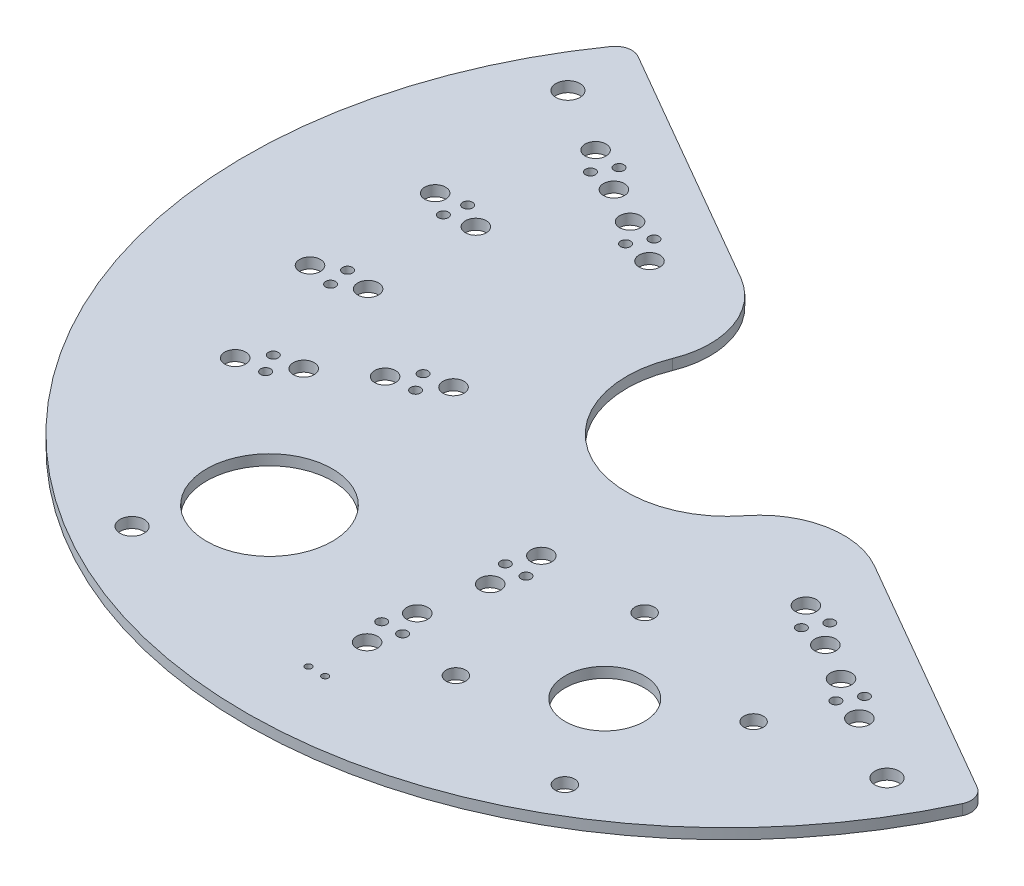
SolidWorks part; units mm, degrees
ref_plane "Front Plane" through (0, 0, 0) normal (0, 0, 1) x (1, 0, 0)
ref_plane "Top Plane" through (0, 0, 0) normal (0, 1, 0) x (1, 0, 0)
ref_plane "Right Plane" through (0, 0, 0) normal (1, 0, 0) x (0, 0, -1)
sketch "Sketch1" plane through (0, 0, 0) normal (0, 1, 0) x (1, 0, 0)
  line L0 (0, 50.8) -> (0, 59.6199) construction
  line L1 (0, 50.8) -> (11.3081, 50.8) construction
  line L2 (0, 0) -> (0, 47) construction
  line L3 (0, 0) -> (-46.286, 8.1615) construction
  line L4 (0, 0) -> (0, 47) construction
  line L5 (0, 0) -> (-46.286, -8.1615) construction
  line L6 (-30.1951, -16.4814) -> (-38.7564, -18.616) construction
  line L7 (1.7716, -33.8648) -> (4.3514, -25.4269) construction
  line L8 (31.2901, -20.38) -> (25.051, -14.141) construction
  line L9 (-31.8057, 17.1605) -> (-38.0448, 23.3996) construction
  circle A0 centre (0, 0) radius 50.8 construction
  circle A1 centre (0, 0) radius 15.24
  circle A2 centre (0, 0) radius 73.025
  circle A3 centre (0, 50.8) radius 6.3 construction
  circle A4 centre (25.4, 43.9941) radius 6.3 construction
  circle A5 centre (43.9941, 25.4) radius 6.3 construction
  circle A6 centre (50.8, 0) radius 6.3 construction
  circle A7 centre (43.9941, -25.4) radius 6.3 construction
  circle A8 centre (25.4, -43.9941) radius 6.3 construction
  circle A9 centre (0, -50.8) radius 6.3 construction
  circle A10 centre (-25.4, -43.9941) radius 6.3 construction
  circle A11 centre (-43.9941, -25.4) radius 6.3 construction
  circle A12 centre (-50.8, 0) radius 6.3 construction
  circle A13 centre (-43.9941, 25.4) radius 6.3 construction
  circle A14 centre (-25.4, 43.9941) radius 6.3 construction
  circle A15 centre (0, 50.8) radius 1.585 construction
  circle A16 centre (-1.585, 50.8) radius 0.75
  circle A17 centre (1.585, 50.8) radius 0.75
  circle A18 centre (0, 50.8) radius 3.8 construction
  circle A19 centre (0, 54.6) radius 1.585
  circle A20 centre (0, 47) radius 1.585
  circle A21 centre (47.285, 27.3) radius 1.585
  circle A22 centre (43.2016, 26.7727) radius 0.75
  circle A23 centre (44.7866, 24.0273) radius 0.75
  circle A24 centre (40.7032, 23.5) radius 1.585
  circle A25 centre (47.285, -27.3) radius 1.585
  circle A26 centre (44.7866, -24.0273) radius 0.75
  circle A27 centre (43.2016, -26.7727) radius 0.75
  circle A28 centre (40.7032, -23.5) radius 1.585
  circle A29 centre (0, -54.6) radius 1.585
  circle A30 centre (1.585, -50.8) radius 0.75
  circle A31 centre (-1.585, -50.8) radius 0.75
  circle A32 centre (0, -47) radius 1.585
  circle A33 centre (-47.285, -27.3) radius 1.585
  circle A34 centre (-43.2016, -26.7727) radius 0.75
  circle A35 centre (-44.7866, -24.0273) radius 0.75
  circle A36 centre (-40.7032, -23.5) radius 1.585
  circle A37 centre (-47.285, 27.3) radius 1.585
  circle A38 centre (-44.7866, 24.0273) radius 0.75
  circle A39 centre (-43.2016, 26.7727) radius 0.75
  circle A40 centre (-40.7032, 23.5) radius 1.585
  circle A41 centre (25.4, 43.9941) radius 20
  circle A42 centre (-25.4, -43.9941) radius 9.525
  circle A43 centre (25.4, -43.9941) radius 6
  circle A44 centre (-46.286, 8.1615) radius 1.585
  circle A45 centre (-50.3035, 7.2604) radius 0.75
  circle A46 centre (-49.753, 10.3822) radius 0.75
  circle A47 centre (-53.7705, 9.4812) radius 1.585
  circle A48 centre (-46.286, -8.1615) radius 1.585
  circle A49 centre (-49.753, -10.3822) radius 0.75
  circle A50 centre (-50.3035, -7.2604) radius 0.75
  circle A51 centre (-53.7705, -9.4812) radius 1.585
  circle A52 centre (-30.191, -16.4817) radius 6.3 construction
  circle A53 centre (-30.191, -16.4817) radius 1.585 construction
  circle A54 centre (-29.3973, -17.8553) radius 0.75
  circle A55 centre (-31.002, -15.1168) radius 0.75
  circle A56 centre (-30.191, -16.4817) radius 3.8 construction
  circle A57 centre (-33.5032, -18.378) radius 1.585
  circle A58 centre (-26.9143, -14.5903) radius 1.585
  circle A59 centre (1.7693, -33.8681) radius 6.3 construction
  circle A60 centre (1.7693, -33.8681) radius 1.585 construction
  circle A61 centre (0.1831, -33.841) radius 0.75
  circle A62 centre (3.3569, -33.8759) radius 0.75
  circle A63 centre (1.7693, -33.8681) radius 3.8 construction
  circle A64 centre (1.8498, -30.0524) radius 1.585
  circle A65 centre (1.7028, -37.651) radius 1.585
  circle A66 centre (31.7545, -18.4007) radius 6.3 construction
  circle A67 centre (31.7545, -18.4007) radius 1.585 construction
  circle A68 centre (30.9859, -19.7885) radius 0.75
  circle A69 centre (32.5067, -17.0026) radius 0.75
  circle A70 centre (31.7545, -18.4007) radius 3.8 construction
  circle A71 centre (28.4231, -16.5382) radius 1.585
  circle A72 centre (35.0633, -20.2353) radius 1.585
  circle A73 centre (-31.9359, 18.6471) radius 6.3 construction
  circle A74 centre (-31.9359, 18.6471) radius 1.585 construction
  circle A75 centre (-32.7045, 17.2593) radius 0.75
  circle A76 centre (-31.1837, 20.0452) radius 0.75
  circle A77 centre (-31.9359, 18.6471) radius 3.8 construction
  circle A78 centre (-35.2672, 20.5095) radius 1.585
  circle A79 centre (-28.627, 16.8125) radius 1.585
  point P50 (0, 0)
  point P84 (0, 0)
  dimension "D1" = 12
  dimension "D2" = 101.6
  dimension "D3" = 3.17
  dimension "D4" = 1.5
  dimension "D5" = 7.6
  dimension "D6" = 6
  dimension "D7" = 3.17
  dimension "D8" = 40
  dimension "D9" = 19.05
  dimension "D10" = 12
  dimension "D11" = 146.05
  dimension "D12" = 30.48
  dimension "D14" = 80
  dimension "D16" = 100
  dimension "D13" = 2
  dimension "D15" = 2
extrude "Boss-Extrude1" add sketch "Sketch1" against normal blind 1.5875
sketch "Sketch2" plane through (0, 0, 0) normal (0, 1, 0) x (1, 0, 0)
  line L0 (0, 0) -> (0, 66.04) construction
  line L1 (0, 0) -> (-57.1923, 33.02) construction
  circle A0 centre (0, 0) radius 66.04 construction
  circle A1 centre (0, 66.04) radius 1.8288 construction
  circle A2 centre (-57.1923, 33.02) radius 1.8288
  circle A3 centre (33.02, 57.1923) radius 1.8288
  circle A4 centre (57.1923, -33.02) radius 1.8288
  circle A5 centre (-33.02, -57.1923) radius 1.8288
  point P17 (0, 0)
  dimension "D1" = 132.08
  dimension "D2" = 3.6576
  dimension "D3" = 2
  dimension "D4" = 60
  dimension "D5" = 4
extrude "Cut-Extrude1" cut sketch "Sketch2" against normal through all
sketch "Sketch3" plane through (0, 0, 0) normal (0, 1, 0) x (1, 0, 0)
  line L0 (-57.1923, 33.02) -> (57.1923, -33.02) construction
  line L1 (-59.5338, 44.6372) -> (68.4238, -29.2392)
  line L2 (-52.7473, 40.719) -> (61.6373, -25.321) construction
  arc A0 (68.4238, -29.2392) -> (-59.5338, 44.6372) centre (0, 0) ccw
  dimension "D1" = 8.89
extrude "Cut-Extrude2" cut sketch "Sketch3" against normal through all
fillet "Fillet1" radius 12.7 2 edges at (15.165, -0.7937, -1.5098) (-6.275, -0.7937, -13.8882)
fillet "Fillet2" radius 2.54 2 edges at (67.2161, -0.7937, 28.542) (-58.3261, -0.7937, -43.9399)
sketch "Sketch4" plane through (0, 0, 0) normal (0, 1, 0) x (1, 0, 0)
  line L0 (0, 0) -> (0, -73.025) construction
  arc A0 (-59.6949, 42.0615) -> (66.2738, -30.6666) centre (0, 0) ccw construction
  circle A1 centre (0, 0) radius 62.23 construction
  circle A2 centre (0, -62.23) radius 0.4953 construction
  circle A3 centre (1.27, -62.23) radius 0.4953
  circle A4 centre (-1.27, -62.23) radius 0.4953
  dimension "D1" = 0.9906
  dimension "D4" = 124.46
  dimension "D2" = 2
  dimension "D3" = 2
extrude "Cut-Extrude3" cut sketch "Sketch4" against normal through all
sketch "Sketch5" plane through (0, -1.5875, 0) normal (0, -1, 0) x (1, 0, 0)
  line L0 (34.4907, 15.2341) -> (45.0238, 21.3018)
  line L1 (-31.0536, -21.3854) -> (-30.5378, -22.2779)
  line L2 (-30.0652, -20.8147) -> (-29.5513, -21.704)
  line L3 (-30.5378, -22.2779) -> (-40.9598, -28.3409)
  line L13 (33.3365, 26.1699) -> (41.5359, 31.0198)
  line L14 (28.0125, 9.134) -> (57.7422, 26.2984)
  line L29 (46.7892, 22.3211) -> (54.7743, 26.9312)
  line L30 (29.0711, 12.1121) -> (33.5009, 14.6639)
  line L31 (6.096, 41.9407) -> (6.096, 51.4811)
  line L32 (32.4795, 23.822) -> (40.9598, 28.3409)
  line L33 (-6.096, 38.6381) -> (-6.096, 51.4811)
  line L34 (4.064, 40.0736) -> (4.064, 49.6426)
  line L35 (-21.9165, -19.6925) -> (-41.5359, -31.0198)
  line L39 (-4.064, 36.8606) -> (-4.064, 49.6426)
  line L40 (-30.4135, 24.5983) -> (-41.5359, 31.0198)
  line L42 (-29.8903, 21.9498) -> (-40.9598, 28.3409)
  line L93 (-25.0455, -19.0828) -> (-29.5513, -21.704)
  arc A0 (1.2946, 63.4357) -> (1.2454, 61.0243) centre (1.27, 62.23) ccw
  arc A1 (-1.1373, 61.0264) -> (-1.1844, 63.4379) centre (-1.27, 62.23) ccw
  arc A2 (-1.1373, 61.0264) -> (-54.0489, -28.3589) centre (0, 0) ccw
  arc A3 (-1.1844, 63.4379) -> (-56.1144, -29.6131) centre (0, 0) ccw
  arc A4 (54.7743, 26.9312) -> (1.2454, 61.0243) centre (0, 0) ccw
  arc A5 (-56.1144, -29.6131) -> (-54.0489, -28.3589) centre (-55.1689, -28.8424) ccw
  arc A6 (6.096, 51.4811) -> (2.3857, 51.7858) centre (0, 0) ccw
  arc A7 (32.4795, 23.822) -> (4.064, 40.0736) centre (0, 0) ccw
  arc A8 (2.3857, 51.7858) -> (2.3071, 49.7553) centre (1.585, 50.8) ccw
  arc A9 (-2.3071, 49.7553) -> (-2.3857, 51.7858) centre (-1.585, 50.8) ccw
  arc A10 (-48.5987, -10.912) -> (-50.5848, -11.342) centre (-49.753, -10.3822) ccw
  arc A11 (-51.4133, -6.6431) -> (-49.4, -6.3679) centre (-50.3035, -7.2604) ccw
  arc A12 (46.0407, 23.8268) -> (44.2429, 22.8796) centre (44.7866, 24.0273) ccw
  arc A13 (41.9358, 26.8756) -> (43.655, 27.959) centre (43.2016, 26.7727) ccw
  arc A14 (-49.4, 6.3679) -> (-51.4133, 6.6431) centre (-50.3035, 7.2604) ccw
  arc A15 (-50.5848, 11.342) -> (-48.5987, 10.912) centre (-49.753, 10.3822) ccw
  arc A16 (57.7422, 26.2984) -> (1.2946, 63.4357) centre (0, 0) ccw
  arc A17 (-2.3857, 51.7858) -> (-6.096, 51.4811) centre (0, 0) ccw
  arc A18 (-2.3071, 49.7553) -> (-4.064, 49.6426) centre (0, 0) ccw
  arc A19 (45.0238, 21.3018) -> (44.2429, 22.8796) centre (0, 0) ccw
  arc A20 (29.0711, 12.1121) -> (-25.0455, -19.0828) centre (2.3366, -4.0471) ccw
  arc A21 (28.0125, 9.134) -> (-21.9165, -19.6925) centre (2.3859, -4.1326) ccw
  arc A22 (46.7892, 22.3211) -> (46.0407, 23.8268) centre (0, 0) ccw
  arc A23 (43.655, 27.959) -> (41.5359, 31.0198) centre (0, 0) ccw
  arc A24 (-46.0407, -23.8268) -> (-44.2429, -22.8796) centre (-44.7866, -24.0273) ccw
  arc A25 (-41.9358, -26.8756) -> (-43.655, -27.959) centre (-43.2016, -26.7727) ccw
  arc A26 (41.9358, 26.8756) -> (40.9598, 28.3409) centre (0, 0) ccw
  circle A27 centre (1.27, 62.23) radius 0.4953
  arc A28 (-43.655, 27.959) -> (-41.9358, 26.8756) centre (-43.2016, 26.7727) ccw
  arc A29 (-44.2429, 22.8796) -> (-46.0407, 23.8268) centre (-44.7866, 24.0273) ccw
  circle A30 centre (-1.27, 62.23) radius 0.4953
  arc A31 (-43.655, -27.959) -> (-41.5359, -31.0198) centre (0, 0) ccw
  circle A32 centre (-26.7727, 43.2016) radius 1.27 [skipped]
  circle A33 centre (-24.0273, 44.7866) radius 1.27 [skipped]
  circle A34 centre (24.0273, 44.7866) radius 1.27 [skipped]
  circle A35 centre (26.7727, 43.2016) radius 1.27 [skipped]
  circle A36 centre (50.8, 1.585) radius 1.27 [skipped]
  circle A37 centre (50.8, -1.585) radius 1.27 [skipped]
  circle A38 centre (44.7866, -24.0273) radius 1.27 [skipped]
  circle A39 centre (43.2016, -26.7727) radius 1.27 [skipped]
  circle A40 centre (26.7727, -43.2016) radius 1.27 [skipped]
  circle A41 centre (24.0273, -44.7866) radius 1.27 [skipped]
  circle A42 centre (1.585, -50.8) radius 1.27 [skipped]
  circle A43 centre (-1.585, -50.8) radius 1.27 [skipped]
  circle A44 centre (-24.0273, -44.7866) radius 1.27 [skipped]
  circle A45 centre (-26.7727, -43.2016) radius 1.27 [skipped]
  circle A46 centre (-50.8, 1.585) radius 1.27 [skipped]
  circle A47 centre (-50.8, -1.585) radius 1.27 [skipped]
  arc A48 (-41.9358, -26.8756) -> (-40.9598, -28.3409) centre (0, 0) ccw
  arc A49 (-40.9598, 28.3409) -> (-41.9358, 26.8756) centre (0, 0) ccw
  arc A50 (33.3365, 26.1699) -> (6.096, 41.9407) centre (0, 0) ccw
  circle A51 centre (1.585, 50.8) radius 0.75
  arc A52 (-46.0407, 23.8268) -> (-47.6319, 20.4612) centre (0, 0) ccw
  arc A53 (4.064, 49.6426) -> (2.3071, 49.7553) centre (0, 0) ccw
  arc A54 (-41.5359, 31.0198) -> (-43.655, 27.959) centre (0, 0) ccw
  arc A55 (-6.096, 38.6381) -> (-30.4135, 24.5983) centre (0, 0) ccw
  arc A56 (-4.064, 36.8606) -> (-29.8903, 21.9498) centre (0, 0) ccw
  arc A57 (-44.2429, 22.8796) -> (-48.5987, 10.912) centre (0, 0) ccw
  circle A58 centre (-1.585, 50.8) radius 0.75
  circle A59 centre (43.2016, 26.7727) radius 0.75
  arc A60 (-47.6319, 20.4612) -> (-50.5848, 11.342) centre (0, 0) ccw
  arc A61 (-51.4133, 6.6431) -> (-51.4133, -6.6431) centre (0, 0) ccw
  arc A62 (-49.4, 6.3679) -> (-49.4, -6.3679) centre (0, 0) ccw
  circle A63 centre (44.7866, 24.0273) radius 0.75
  arc A64 (-50.5848, -11.342) -> (-46.0407, -23.8268) centre (0, 0) ccw
  arc A65 (-48.5987, -10.912) -> (-44.2429, -22.8796) centre (0, 0) ccw
  circle A66 centre (-43.2016, 26.7727) radius 0.75
  circle A67 centre (-44.7866, 24.0273) radius 0.75
  circle A68 centre (-49.753, 10.3822) radius 0.75
  circle A69 centre (-50.3035, 7.2604) radius 0.75
  circle A70 centre (-50.3035, -7.2604) radius 0.75
  circle A71 centre (-49.753, -10.3822) radius 0.75
  circle A72 centre (-44.7866, -24.0273) radius 0.75
  circle A73 centre (-43.2016, -26.7727) radius 0.75
  arc A74 (29.7503, 20.2948) -> (30.8424, 21.1896) centre (30.9918, 19.8934) ccw
  arc A75 (4.5236, 34.6192) -> (30.8424, 21.1896) centre (5.7054, 4.4312) cw
  arc A76 (4.4841, 33.194) -> (29.7503, 20.2948) centre (4.8534, 2.7227) cw
  arc A77 (33.7473, 16.7292) -> (32.8413, 15.8053) centre (32.514, 17.0324) ccw
  arc A78 (33.5009, 14.6639) -> (32.8413, 15.8053) centre (-9.9501, -9.686) ccw
  arc A79 (34.4907, 15.2341) -> (33.7473, 16.7292) centre (-12.2934, -7.0976) ccw
  arc A80 (-0.8928, 32.9745) -> (-0.4432, 34.9562) centre (0.075, 33.7967) ccw
  arc A81 (-29.697, 19.0828) -> (-0.4432, 34.9562) centre (2.1808, -4.7732) cw
  arc A82 (4.5236, 34.6192) -> (4.4841, 33.194) centre (3.4532, 33.9357) ccw
  circle A83 centre (-31.1738, -20.0389) radius 0.75
  arc A84 (-29.697, 19.0828) -> (-28.1584, 17.7555) centre (-29.4254, 17.8422) ccw
  arc A85 (-28.1584, 17.7555) -> (-0.8928, 32.9745) centre (0.881, -2.2367) cw
  arc A86 (-31.3368, 13.0383) -> (-32.985, 14.2011) centre (-31.3367, 14.7878) ccw
  arc A87 (-32.985, 14.2011) -> (-34.3304, 11.6344) centre (112.8254, -63.8668) ccw
  arc A88 (-33.9153, -16.8172) -> (-31.9293, -16.3872) centre (-32.7611, -17.3469) ccw
  arc A89 (-31.9293, -16.3872) -> (-32.6415, -14.9048) centre (-79.0072, -38.0929) ccw
  arc A90 (-30.0652, -20.8147) -> (-31.0536, -21.3854) centre (-31.1268, -20.1175) ccw
  circle A91 centre (-32.7183, -17.2601) radius 0.75
  arc A92 (-34.3304, 11.6344) -> (-33.9153, -16.8172) centre (-7.3644, -2.2011) ccw
  arc A93 (-31.3368, 13.0383) -> (-32.6415, -14.9048) centre (-7.0347, -2.0984) ccw
  circle A94 centre (-31.007, 15.1229) radius 0.75
  circle A95 centre (-29.3984, 17.8491) radius 0.75
  circle A96 centre (0.1843, 33.8387) radius 0.75
  circle A97 centre (3.3549, 33.875) radius 0.75
  circle A98 centre (30.9845, 19.7892) radius 0.75
  circle A99 centre (32.5074, 16.9933) radius 0.75
  dimension "D13" = 12
  dimension "D15" = 3
extrude "Boss-Extrude2" add sketch "Sketch5" along normal blind 0.1016
sketch "Sketch6" plane through (0, -1.5875, 0) normal (0, -1, 0) x (1, 0, 0)
  line L0 (0, 0) -> (25.4, 43.9941) construction
  line L1 (25.4, 43.9941) -> (36.5125, 63.2415) construction
  circle A0 centre (25.4, 43.9941) radius 16.51 construction
  arc A1 (66.2738, 30.6666) -> (-59.6949, -42.0615) centre (0, 0) ccw construction
  circle A2 centre (33.655, 58.2922) radius 1.4732
  circle A3 centre (11.1019, 52.2491) radius 1.4732
  circle A4 centre (17.145, 29.696) radius 1.4732
  circle A5 centre (39.6981, 35.7391) radius 1.4732
  point P20 (25.4, 43.9941)
  dimension "D1" = 2.9464
extrude "Cut-Extrude4" cut sketch "Sketch6" against normal through all
